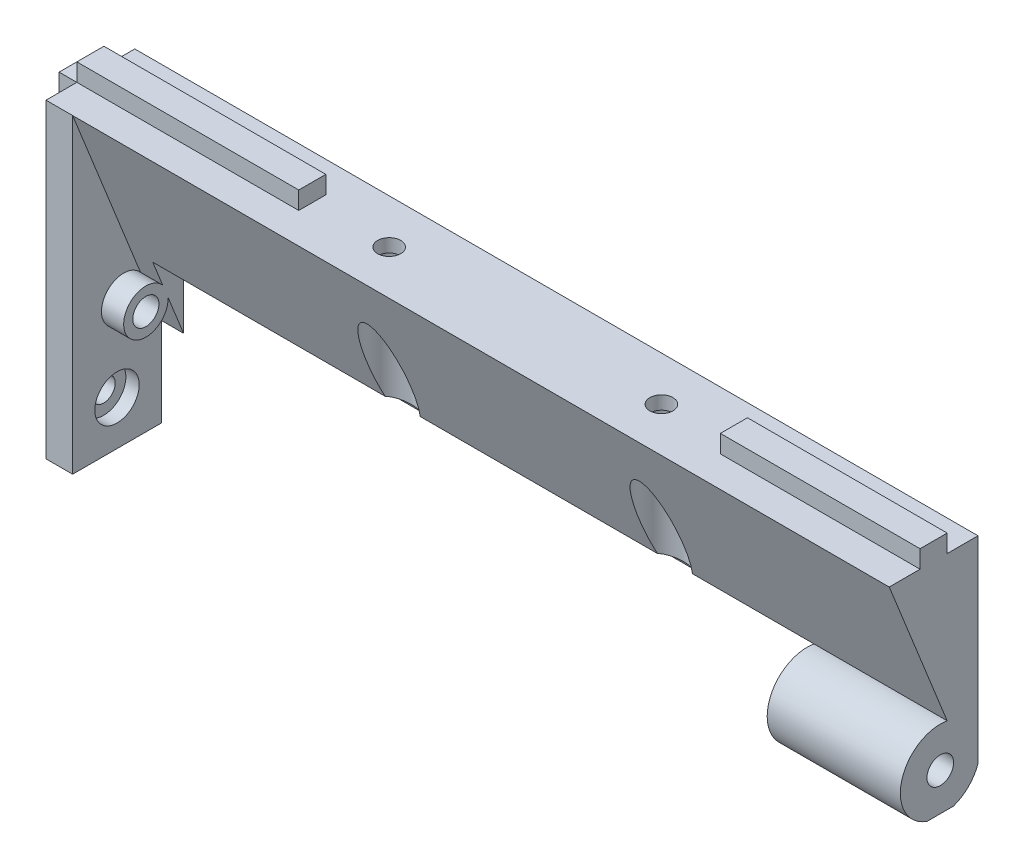
SolidWorks part; units mm, degrees
ref_plane "前视基准面" through (0, 0, 0) normal (0, 0, 1) x (1, 0, 0)
ref_plane "上视基准面" through (0, 0, 0) normal (0, 1, 0) x (1, 0, 0)
ref_plane "右视基准面" through (0, 0, 0) normal (1, 0, 0) x (0, 0, -1)
other "Configuration Table"
sketch "草图1" plane through (0, 0, 0) normal (0, 1, 0) x (1, 0, 0)
  line L1 (0, 0) -> (120, 0)
  line L2 (0, 0) -> (0, 20)
  line L3 (0, 20) -> (120, 20)
  line L4 (120, 0) -> (120, 20)
extrude "凸台-拉伸1" add sketch "草图1" along normal blind 50
sketch "草图2" plane through (0, 0, 0) normal (0, 0, 1) x (1, 0, 0)
  line L1 (0, 0) -> (6, 0)
  line L2 (0, 0) -> (0, -20)
  line L3 (0, -20) -> (6, -20)
  line L4 (6, 0) -> (6, -20)
extrude "凸台-拉伸2" add sketch "草图2" against normal blind 20
sketch "草图3" plane through (120, 0, 0) normal (1, 0, 0) x (0, 0, -1)
  line L0 (0, 50) -> (20, 0)
  line L1 (20, 0) -> (0, 0)
  line L2 (0, 0) -> (0, 50)
extrude "切除-拉伸1" cut sketch "草图3" against normal blind 114 contours L2 L0 L1
sketch "草图4" plane through (6, 0, 0) normal (1, 0, 0) x (0, 0, -1)
  line L4 (20, 0) -> (0, 0)
  line L5 (20, 0) -> (20, -20)
  line L6 (20, -20) -> (0, -20)
  line L7 (0, 0) -> (0, -20)
  circle A0 centre (10, 10) radius 2.6
extrude "切除-拉伸2" cut sketch "草图4" against normal blind 114 contours A0 | L5 L4 L7 L6
sketch "草图5" plane through (6, 0, 0) normal (1, 0, 0) x (0, 0, -1)
  circle A0 centre (10, 10) radius 5
extrude "切除-拉伸3" cut sketch "草图5" against normal blind 3
sketch "草图9" plane through (0, 50, 0) normal (0, 1, 0) x (1, 0, 0)
  circle A0 centre (60, 10) radius 5
  circle A1 centre (60, 10) radius 2.6
extrude "凸台-拉伸3" add sketch "草图9" against normal blind 3
sketch "草图11" plane through (6, 0, 0) normal (1, 0, 0) x (0, 0, -1)
  circle A0 centre (10, 10) radius 5
extrude "凸台-拉伸4" add sketch "草图11" against normal blind 6
sketch "草图12" plane through (0, 0, 0) normal (-1, 0, 0) x (0, 0, 1)
  line L0 (-20, 0) -> (-11.5, 0)
  line L1 (-20, 0) -> (0, 0) construction
  line L2 (-11.5, 0) -> (-11.5, 8.5)
  circle A0 centre (-11.5, 8.5) radius 3
extrude "切除-拉伸6" cut sketch "草图12" against normal blind 6 contours A0 region at (0, 6.4387, -9.4387)
sketch "草图13" plane through (120, 0, 0) normal (1, 0, 0) x (0, 0, -1)
  line L5 (20, 0) -> (20, 11.458)
  line L7 (20, 50) -> (20, 0) construction
  line L8 (0, 50) -> (20, 0) construction
  line L9 (13.0541, 17.3648) -> (20, 0)
  arc A2 (20, 11.458) -> (13.0541, 17.3648) centre (11.5, 8.5) ccw
extrude "切除-拉伸8" cut sketch "草图13" against normal blind 109
sketch "草图14" plane through (0, 0, 0) normal (-1, 0, 0) x (0, 0, 1)
  line L1 (-20, 0) -> (0, 0)
  line L2 (-20, 0) -> (-20, -20)
  line L3 (-20, -20) -> (0, -20)
  line L4 (0, 0) -> (0, -20)
  circle A0 centre (-10, -10) radius 2.6
extrude "凸台-拉伸5" add sketch "草图14" against normal blind 6
sketch "草图15" plane through (6, 0, 0) normal (1, 0, 0) x (0, 0, -1)
  circle A0 centre (10, -10) radius 5
extrude "切除-拉伸9" cut sketch "草图15" against normal blind 3
sketch "草图18" plane through (6, 0, 0) normal (1, 0, 0) x (0, 0, -1)
  circle A1 centre (11.5, 8.5) radius 3
  circle A2 centre (11.5, 8.5) radius 5
  circle M3 centre (11.5, 8.5) radius 3
extrude "凸台-拉伸6" add sketch "草图18" along normal blind 5 contours M3 | A2 region at (6, 8.5, -11.5)
sketch "草图19" plane through (0, 0, 0) normal (-1, 0, 0) x (0, 0, 1)
  circle A0 centre (-11.5, 8.5) radius 3
  circle A1 centre (-11.5, 8.5) radius 2.95
extrude "凸台-拉伸7" add sketch "草图19" against normal blind 11
sketch "草图20" plane through (120, 0, 0) normal (1, 0, 0) x (0, 0, -1)
  line L0 (0, 50) -> (20, 50)
  line L1 (20, 50) -> (20, 11.458)
  line L2 (0, 50) -> (13.0541, 17.3648)
  arc A0 (13.0541, 17.3648) -> (20, 11.458) centre (11.5, 8.5) cw
extrude "凸台-拉伸8" add sketch "草图20" along normal blind 70
sketch "草图22" plane through (0, 0, 0) normal (-1, 0, 0) x (0, 0, 1)
  line L0 (-10, 50) -> (-10, 11.45)
  line L1 (-20, 50) -> (0, 50) construction
  line L2 (-10, 11.45) -> (-6.95, 11.45)
  line L3 (-10, 50) -> (-13.05, 50)
  line L5 (-13.05, 50) -> (-6.95, 50)
  line L6 (-13.05, 50) -> (-13.05, 11.45)
  line L7 (-13.05, 11.45) -> (-6.95, 11.45)
  line L8 (-6.95, 50) -> (-6.95, 11.45)
  line M10 (0, 50) -> (-20, 50)
extrude "凸台-拉伸9" add sketch "草图22" along normal blind 4 contours L8 L0 L2 M10 | L6 L7 L0 M10 region at (0, 30.725, -8.475) region at (0, 30.725, -11.525)
sketch "草图24" plane through (0, 50, 0) normal (0, 1, 0) x (1, 0, 0)
  line L0 (190, 20) -> (0, 20) construction
  line L1 (190, 0) -> (160, 0)
  line L2 (190, 0) -> (190, 20)
  line L3 (190, 20) -> (160, 20)
  line L4 (160, 0) -> (160, 20)
extrude "凸台-拉伸10" add sketch "草图24" against normal blind 50
sketch "草图25" plane through (0, 0, 0) normal (-1, 0, 0) x (0, 0, 1)
  circle A0 centre (-11.5, 8.5) radius 2.95
extrude "切除-拉伸10" cut sketch "草图25" against normal blind 200
sketch "草图27" plane through (0, 6.8966, -17.2414) normal (0, -0.3714, 0.9285) x (1, 0, 0)
  line L0 (6, 46.4238) -> (160, 46.4238)
sketch "草图28" plane through (0, 50, 0) normal (0, 1, 0) x (1, 0, 0)
  line L0 (128.67, 0) -> (128.67, 20)
  line L1 (98, 10) -> (67.33, 10)
  line L2 (190, 20) -> (0, 20) construction
  line L3 (98, 10) -> (128.67, 10)
  line L5 (67.33, 20) -> (67.33, 0)
  line L6 (6, 0) -> (160, 0) construction
  line L7 (6, 0) -> (190, 0)
  line L8 (98, 0) -> (98, 20)
  circle A0 centre (67.33, 10) radius 5
  circle A1 centre (128.67, 10) radius 5
extrude "切除-拉伸11" cut sketch "草图28" against normal blind 200 contours L5 A0 | L5 A0 | L0 A1 | L0 A1 rebuild error yes
sketch "草图30" plane through (0, 50, 0) normal (0, 1, 0) x (1, 0, 0)
  circle A0 centre (57.33, 10) radius 5
  circle A1 centre (57.33, 10) radius 2.6
  circle A2 centre (108.67, 10) radius 5
  circle A3 centre (108.67, 10) radius 2.6
extrude "凸台-拉伸11" add sketch "草图30" against normal blind 3 contours A0 | A1 | A2 | A3
sketch "草图32" plane through (190, 0, 0) normal (1, 0, 0) x (0, 0, -1)
  circle A0 centre (11.5, 8.5) radius 3
extrude "切除-拉伸12" cut sketch "草图32" against normal blind 30
sketch "草图34" plane through (160, 0, 0) normal (-1, 0, 0) x (0, 0, 1)
  line L0 (0, 50) -> (-13.0541, 17.3648)
  line L1 (-20, 0) -> (-20, 11.458) construction
  line L2 (0, 50) -> (0, 0)
  line L3 (0, 0) -> (-20, 0)
  line L4 (-20, 0) -> (-20, 5.542)
  arc A0 (-20, 11.458) -> (-13.0541, 17.3648) centre (-11.5, 8.5) cw
  arc A1 (-13.0541, 17.3648) -> (-20, 5.542) centre (-11.5, 8.5) cw
  line M2 (0, 0) -> (0, 50)
  line M3 (0, 50) -> (-13.0541, 17.3648)
  line M5 (-20, 11.458) -> (-20, 0)
  line M6 (-20, 0) -> (0, 0)
extrude "切除-拉伸13" cut sketch "草图34" against normal blind 30 contours A1 M3 M6 M2 | A1 M6 M5 region at (160, 23.2807, -3.8647) region at (160, 1.5488, -18.4512)
sketch "草图35" plane through (0, 50, 0) normal (0, 1, 0) x (1, 0, 0)
  line L0 (6, 0) -> (190, 0)
  line L1 (98, 0) -> (98, 20)
  line L2 (190, 20) -> (0, 20) construction
  line L3 (98, 10) -> (128.67, 10)
  line L4 (98, 10) -> (67.33, 10)
  circle A0 centre (67.33, 10) radius 5
  circle A1 centre (128.67, 10) radius 5
extrude "切除-拉伸14" cut sketch "草图35" against normal blind 60 contours A0 | A1 region at (128.67, 50, -14.8586) region at (62.4714, 50, -10)
sketch "草图36" plane through (0, 50, 0) normal (0, 1, 0) x (1, 0, 0)
  circle A0 centre (67.33, 10) radius 5
  circle A1 centre (67.33, 10) radius 2.6
  circle A2 centre (128.67, 10) radius 5
  circle A3 centre (128.67, 10) radius 2.6
extrude "凸台-拉伸12" add sketch "草图36" against normal blind 3
sketch "草图37" plane through (0, 50, 0) normal (0, 1, 0) x (1, 0, 0)
  line L0 (190, 13.0541) -> (190, 6.95)
  line L1 (-4, 13.05) -> (0, 13.05)
  line L2 (-4, 13.05) -> (-4, 6.95)
  line L3 (-4, 6.95) -> (0, 6.95)
  line L4 (0, 13.05) -> (0, 6.95)
  line L5 (0, 6.95) -> (50, 6.95)
  line L6 (0, 6.95) -> (0, 13.05)
  line L7 (0, 13.05) -> (50, 13.05)
  line L8 (50, 6.95) -> (50, 13.05)
  line L10 (50, 6.95) -> (50, 13.0541)
  line L13 (190, 13.0541) -> (145, 13.0541)
  line L15 (190, 6.95) -> (145, 6.95)
  line L16 (145, 13.0541) -> (145, 6.95)
  line M15 (190, 0) -> (190, 20)
extrude "凸台-拉伸13" add sketch "草图37" along normal blind 4 contours L5 L8 L7 L4 | L13 L16 L15 M15 region at (167.5, 50, -10.002) region at (25, 50, -10)
